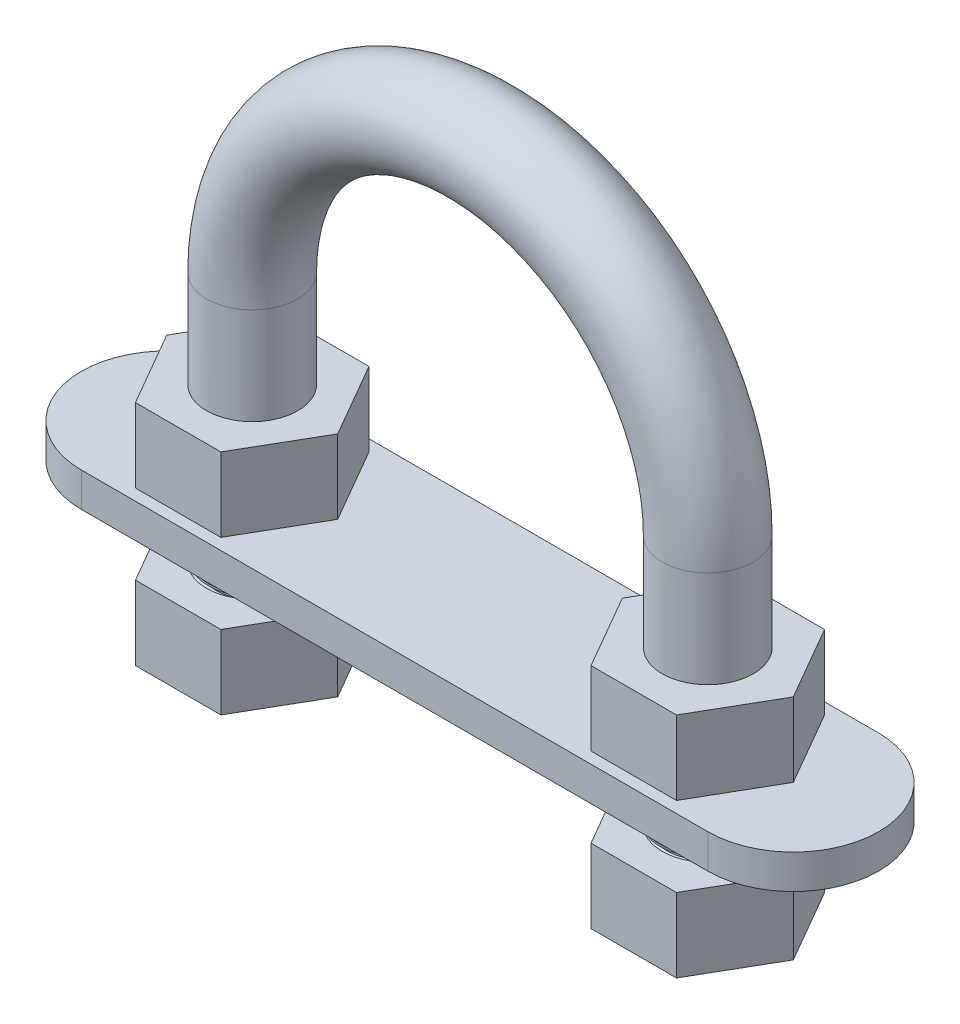
SolidWorks part; units mm, degrees
material "Dökme Paslanmaz Çelik"
ref_plane "Ön Düzlem" through (0, 0, 0) normal (0, 0, 1) x (1, 0, 0)
ref_plane "Üst Düzlem" through (0, 0, 0) normal (0, 1, 0) x (1, 0, 0)
ref_plane "Sağ Düzlem" through (0, 0, 0) normal (1, 0, 0) x (0, 0, -1)
sketch "Çizim1" plane through (0, 0, 0) normal (0, 0, 1) x (1, 0, 0)
  line L0 (20, 0) -> (-20, 0) construction
  line L1 (-20, 0) -> (-20, 35)
  line L2 (20, 0) -> (20, 35)
  line L3 (0, 0) -> (0, 70) construction
  line L4 (-20, 35) -> (-20, 50)
  line L5 (20, 35) -> (20, 50)
  arc A0 (20, 50) -> (-20, 50) centre (0, 50) ccw
  point P4 (0, 0)
  dimension "D5" = 40
  dimension "D1" = 40
  dimension "D2" = 35
  dimension "D3" = 70
  dimension "D4" = 35
ref_plane "Düzlem1" through (-20, 0, 0) normal (0, -1, 0) x (-1, 0, 0)
sketch "Çizim2" plane through (-20, 0, 0) normal (0, -1, 0) x (-1, 0, 0)
  circle A0 centre (0, 0) radius 4
  dimension "D1" = 8
sweep "Süpür2" add profiles "Çizim2" path "Çizim1"
ref_plane "Düzlem2" through (0, 35, 0) normal (0, -1, 0) x (-1, 0, 0)
sketch "Çizim3" plane through (0, 35, 0) normal (0, -1, 0) x (-1, 0, 0)
  line L0 (-20, 0) -> (20, 0) construction
  line L1 (23.7528, 6.5) -> (16.2472, 6.5)
  line L2 (16.2472, 6.5) -> (12.4944, 0)
  line L3 (12.4944, 0) -> (16.2472, -6.5)
  line L4 (16.2472, -6.5) -> (23.7528, -6.5)
  line L5 (23.7528, -6.5) -> (27.5056, 0)
  line L6 (27.5056, 0) -> (23.7528, 6.5)
  circle A0 centre (20, 0) radius 6.5 construction
  dimension "D1" = 13
extrude "Yükseklik-Ekstrüzyon1" add sketch "Çizim3" against normal blind 6.5
mirror "Aynalama1" about plane through (0, 0, 0) normal (1, 0, 0) of "Yükseklik-Ekstrüzyon1"
sketch "Çizim4" plane through (0, 35, 0) normal (0, -1, 0) x (1, 0, 0)
  line L0 (27.5056, 0) -> (-27.5056, 0) construction
  line L1 (27.5056, -7.5) -> (-27.5056, -7.5)
  line L2 (27.5056, 7.5) -> (-27.5056, 7.5)
  line L3 (0, 0) -> (0, 7.5) construction
  arc A0 (27.5056, -7.5) -> (27.5056, 7.5) centre (27.5056, 0) ccw
  arc A1 (-27.5056, 7.5) -> (-27.5056, -7.5) centre (-27.5056, 0) ccw
  circle A2 centre (-20, 0) radius 4 construction
  circle A3 centre (-20, 0) radius 4 construction
  circle A4 centre (-20, 0) radius 4.5
  circle A5 centre (20, 0) radius 4.5
  point P2 (0, 0)
  dimension "D1" = 7.5
  dimension "D2" = 0.5
extrude "Yükseklik-Ekstrüzyon2" add sketch "Çizim4" along normal blind 3
ref_plane "Düzlem3" through (0, 31.5, 0) normal (0, -1, 0) x (-1, 0, 0)
mirror "Aynalama2" about plane through (0, 31.5, 0) normal (0, -1, 0) of "Aynalama1", "Yükseklik-Ekstrüzyon1"
thread "Diş1" pitch 1.25 method cut profile "Diş Profili1" start angle 0, offset 0, length 0, pitch 1.25, diameter 8
ref_plane "Düzlem4" through (24, 0, 0) normal (0, 0, 1) x (1, 0, 0)
sketch "Diş Profili1" plane through (24, 0, 0) normal (0, 0, 1) x (1, 0, 0)
  line L0 (0, 0) -> (0, 1.25) construction
  line L11 (0, 0) -> (0, 1.0937)
  line L12 (0, 1.0937) -> (-0.6766, 0.7031)
  line L13 (-0.6766, 0.7031) -> (-0.6766, 0.3906)
  line L15 (-0.6766, 0.3906) -> (0, 0)
  line L17 (-0.6766, 0.5469) -> (0, 0.5469) construction
  point P2 (0, 0)
  dimension "Pitch" = 1.25
  dimension "Profile_Angle" = 60
  dimension "Profile_Land" = 0.3125
  dimension "Profile_Height" = 0.6766
mirror "Aynalama3" about plane through (0, 0, 0) normal (1, 0, 0) of "Diş1"
sketch "Çizim5" plane through (0, 0, 0) normal (0, -1, 0) x (1, 0, 0)
  circle A0 centre (0, 0) radius 36.9784
extrude "Kes-Ekstrüzyon1" cut sketch "Çizim5" against normal blind 21
